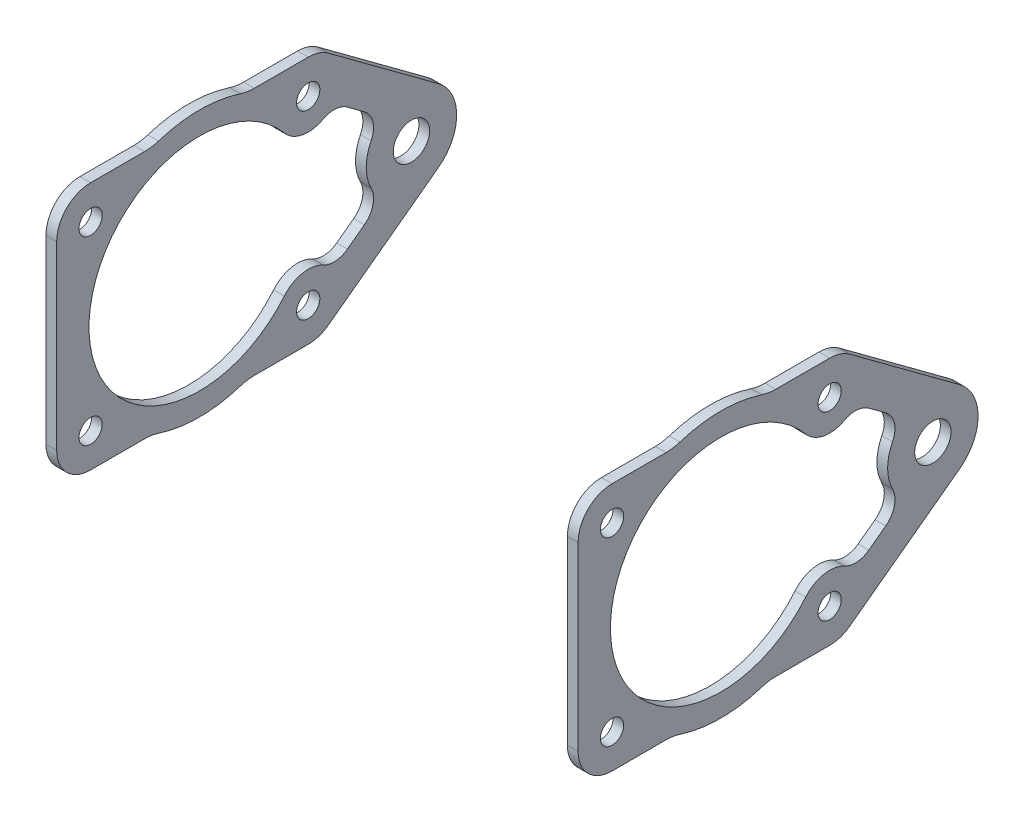
SolidWorks part; units mm, degrees
ref_plane "Front Plane" through (0, 0, 0) normal (0, 0, 1) x (1, 0, 0)
ref_plane "Top Plane" through (0, 0, 0) normal (0, 1, 0) x (1, 0, 0)
ref_plane "Right Plane" through (0, 0, 0) normal (1, 0, 0) x (0, 0, -1)
sketch "Sketch1" plane through (37.35, 0, 0) normal (-1, 0, 0) x (0, 0, 1)
  line L0 (-3.7778, 5.104) -> (11.6564, 16.528)
  line L1 (14.4897, 17.4625) -> (45.0415, 17.4625)
  line L2 (49.804, 12.7) -> (49.804, -12.7)
  line L4 (45.0415, -17.4625) -> (14.4897, -17.4625)
  line L5 (11.6564, -16.528) -> (-3.7778, -5.104)
  line L7 (8.9922, -8.6309) -> (6.6044, -6.8635)
  line L8 (6.6044, 6.8635) -> (8.9922, 8.6309)
  arc A1 (17.8467, -9.9091) -> (17.8467, 9.9091) centre (29.7656, 0) ccw
  arc A2 (5.6622, 2.8743) -> (5.6622, -2.8743) centre (0, 0) cw
  arc A3 (-3.7778, 5.104) -> (-3.7778, -5.104) centre (0, 0) ccw
  arc A5 (12.4005, -8.8667) -> (17.8467, -9.9091) centre (14.4897, -12.7) cw
  arc A6 (17.8467, 9.9091) -> (12.4005, 8.8667) centre (14.4897, 12.7) cw
  arc A7 (12.4005, -8.8667) -> (8.9922, -8.6309) centre (10.8811, -6.0789) cw
  arc A8 (6.6044, -6.8635) -> (5.6622, -2.8743) centre (8.4933, -4.3115) cw
  arc A9 (11.6564, -16.528) -> (14.4897, -17.4625) centre (14.4897, -12.7) ccw
  arc A10 (45.0415, -17.4625) -> (49.804, -12.7) centre (45.0415, -12.7) ccw
  arc A11 (49.804, 12.7) -> (45.0415, 17.4625) centre (45.0415, 12.7) ccw
  arc A12 (14.4897, 17.4625) -> (11.6564, 16.528) centre (14.4897, 12.7) ccw
  arc A13 (42.335, -16.6187) -> (47.4198, -8.5739) centre (45.0415, -12.7) ccw construction
  arc A14 (47.4198, 8.5739) -> (42.335, 16.6187) centre (45.0415, 12.7) ccw construction
  arc A15 (17.1962, 16.6187) -> (12.1114, 8.5739) centre (14.4897, 12.7) ccw construction
  arc A16 (12.1114, -8.5739) -> (17.1962, -16.6187) centre (14.4897, -12.7) ccw construction
  arc A17 (5.6622, 2.8743) -> (6.6044, 6.8635) centre (8.4933, 4.3115) cw
  arc A18 (8.9922, 8.6309) -> (12.4005, 8.8667) centre (10.8811, 6.0789) cw
  circle A19 centre (14.4897, 12.7) radius 1.632 construction
  circle A20 centre (14.4897, 12.7) radius 1.632
  circle A21 centre (45.0415, 12.7) radius 1.632 construction
  circle A22 centre (45.0415, -12.7) radius 1.632 construction
  circle A23 centre (14.4897, -12.7) radius 1.632 construction
  circle A24 centre (45.0415, 12.7) radius 1.6319
  circle A25 centre (45.0415, -12.7) radius 1.6319
  circle A26 centre (14.4897, -12.7) radius 1.632
  circle A27 centre (29.7656, 0) radius 15.5 construction
  dimension "D1" = 6.35
  dimension "D2" = 3.175
  dimension "D3" = 4.7625
  dimension "D4" = 4.7625
extrude "Boss-Extrude1" add sketch "Sketch1" along normal blind 1.5
sketch "Sketch4" plane through (35.85, 0, 0) normal (-1, 0, 0) x (0, 0, 1)
  line L0 (23.1462, 17.4625) -> (36.385, 17.4625)
  line L1 (45.0415, 17.4625) -> (14.4897, 17.4625) construction
  line L2 (23.1462, -17.4625) -> (36.385, -17.4625)
  line L3 (14.4897, -17.4625) -> (45.0415, -17.4625) construction
  arc A0 (23.1462, -17.4625) -> (36.385, -17.4625) centre (29.7656, 0) ccw
  arc A1 (36.385, 17.4625) -> (23.1462, 17.4625) centre (29.7656, 0) ccw
  arc A2 (17.8467, -9.9091) -> (17.8467, 9.9091) centre (29.7656, 0) ccw construction
  dimension "D1" = 3.175
extrude "Boss-Extrude2" add sketch "Sketch4" against normal up to surface (1.5 mm away) up to face at (37.35, 0, 23.3678)
fillet "Fillet1" radius 6.35 4 edges at (36.6, -17.4625, 23.1462) (36.6, -17.4625, 36.385) (36.6, 17.4625, 23.1462) (36.6, 17.4625, 36.385)
hole_wizard "#10 Clearance Hole1" positions "Sketch2" profile "Sketch3" hole size "#10" standard "ANSI Inch" end condition up to next
sketch "Sketch2" plane through (35.85, 0, 0) normal (-1, 0, 0) x (0, 0, 1)
  point P0 (0, 0)
sketch "Sketch3" plane through (35.85, 0, 0) normal (0, 1, 0) x (0, 0, 1)
  line L0 (0, 0) -> (0, 1.5)
  line L1 (0, 1.5) -> (2.5527, 1.5)
  line L2 (2.5527, 1.5) -> (2.5527, 0)
  line L5 (2.5527, 0) -> (0, 0)
  line L11 (0, -6.35) -> (0, 107.95) construction
  dimension "Thru Hole Dia." = 5.1054
  dimension "Thru Hole Depth" = 1.5
mirror "Mirror2" about plane through (0, 0, 0) normal (1, 0, 0) of bodies 102
equation "\"D1@Boss-Extrude1\"=1.5mm"
equation "\"D3@Sketch1\"=\"D4@Sketch1\""
